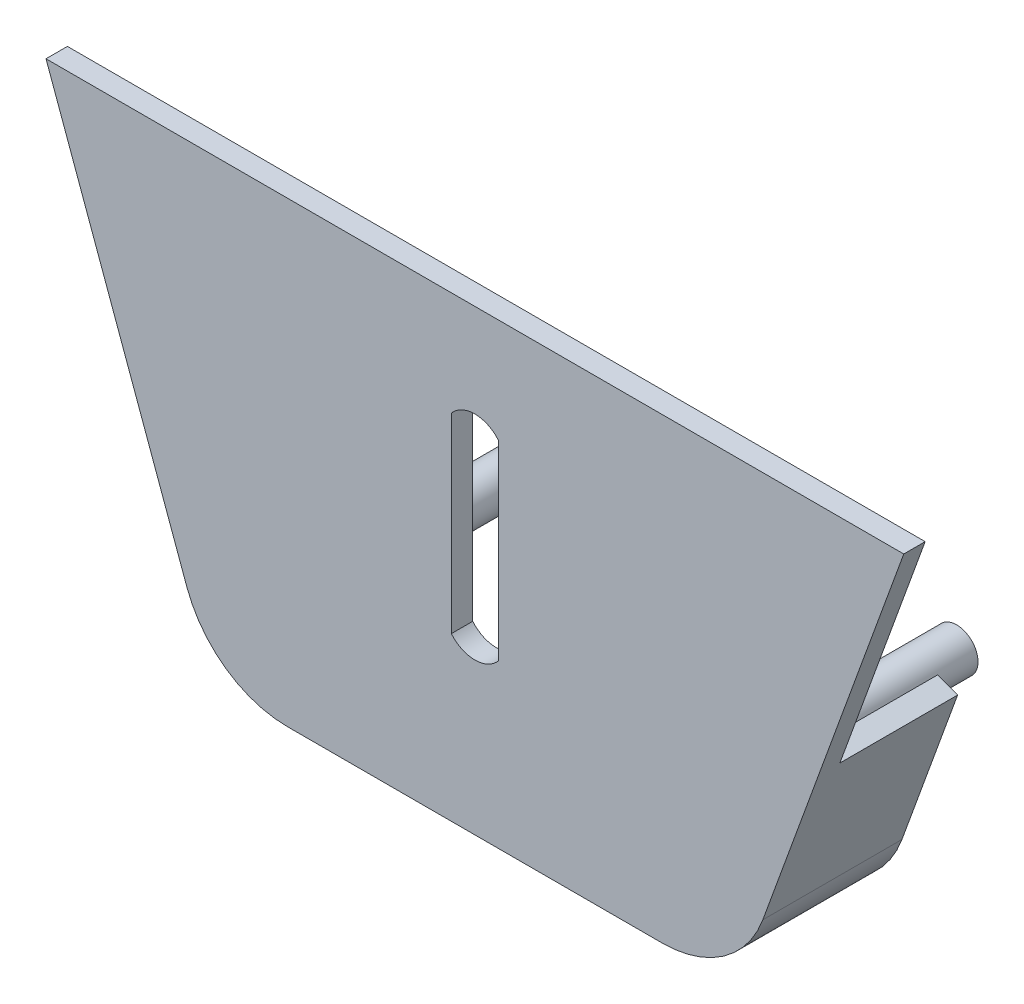
SolidWorks part; units mm, degrees
ref_plane "Front Plane" through (0, 0, 0) normal (0, 0, 1) x (1, 0, 0)
ref_plane "Top Plane" through (0, 0, 0) normal (0, 1, 0) x (1, 0, 0)
ref_plane "Right Plane" through (0, 0, 0) normal (1, 0, 0) x (0, 0, -1)
sketch "Sketch1" plane through (0, 0, 0) normal (0, 0, 1) x (1, 0, 0)
  line L0 (-17.5, 0) -> (17.5, 0) construction
  line L1 (-17.5, -10) -> (17.5, -10)
  line L2 (-26.8969, -3.4202) -> (-40.0654, 32.76)
  line L3 (-40.0654, 32.76) -> (40.0654, 32.76)
  line L4 (40.0654, 32.76) -> (26.8969, -3.4202)
  line L5 (40.0654, 32.76) -> (-40.0654, 32.76) construction
  line L6 (26.8969, -3.4202) -> (40.0654, 32.76) construction
  line L7 (-40.0654, 32.76) -> (-30.3893, 6.1749) construction
  line L8 (0, 21.1909) -> (0, 7.0144) construction
  line L9 (2.8635, 21.1909) -> (2.8635, 7.0144)
  line L10 (-2.8635, 21.1909) -> (-2.8635, 7.0144)
  arc A0 (-26.8969, -3.4202) -> (-17.5, -10) centre (-17.5, 0) ccw
  arc A1 (17.5, -10) -> (26.8969, -3.4202) centre (17.5, 0) ccw
  circle A2 centre (17.5, 0) radius 2 construction
  circle A3 centre (17.5, 0) radius 2
  circle A4 centre (-17.5, 0) radius 2 construction
  circle A5 centre (-17.5, 0) radius 2
  arc A6 (2.8635, 21.1909) -> (-2.8635, 21.1909) centre (0, 21.1909) ccw
  arc A9 (-2.8635, 7.0144) -> (2.8635, 7.0144) centre (0, 7.0144) ccw
  point P13 (0, 14.1027)
  dimension "D3" = 20
  dimension "D4" = 20
  dimension "D1" = 35
  dimension "D2" = 17.5
extrude "Boss-Extrude1" add sketch "Sketch1" along normal blind 2
sketch "Sketch2" plane through (0, 0, 2) normal (0, 0, 1) x (1, 0, 0)
  circle A0 centre (-17.5, 0) radius 2 construction
  circle A1 centre (-17.5, 0) radius 2
  circle A2 centre (-17.5, 0) radius 3.5
  circle A3 centre (17.5, 0) radius 2 construction
  circle A4 centre (17.5, 0) radius 2
  circle A5 centre (17.5, 0) radius 3.5
  dimension "D1" = 1.5
  dimension "D2" = 1.5
extrude "Boss-Extrude2" add sketch "Sketch2" against normal blind 4 from vertex starting at point (-17.5, -10, 0)
sketch "Sketch4" plane through (0, 0, 0) normal (0, 0, -1) x (-1, 0, 0)
  line L0 (-39.1029, 10.8636) -> (39.5724, 10.8636) construction
  line L1 (-26.8969, -3.4202) -> (-40.0654, 32.76) construction
  line L2 (-26.8969, -3.4202) -> (-32.0958, 10.8636)
  line L3 (40.0654, 32.76) -> (26.8969, -3.4202) construction
  line L4 (32.0958, 10.8636) -> (26.8969, -3.4202)
  line L5 (-25.0175, -2.7362) -> (-30.2164, 11.5477)
  line L6 (30.2164, 11.5477) -> (25.0175, -2.7362)
  line L7 (-32.0958, 10.8636) -> (-30.2164, 11.5477)
  line L8 (30.2164, 11.5477) -> (32.0958, 10.8636)
  line L9 (17.5, -8) -> (17.5, -10)
  line L10 (-17.5, -10) -> (-17.5, -8)
  arc A0 (-26.8969, -3.4202) -> (-17.5, -10) centre (-17.5, 0) ccw construction
  arc A1 (-26.8969, -3.4202) -> (-17.5, -10) centre (-17.5, 0) ccw
  arc A2 (17.5, -10) -> (26.8969, -3.4202) centre (17.5, 0) ccw construction
  arc A3 (17.5, -10) -> (26.8969, -3.4202) centre (17.5, 0) ccw
  arc A4 (-25.0175, -2.7362) -> (-17.5, -8) centre (-17.5, 0) ccw
  arc A5 (17.5, -8) -> (25.0175, -2.7362) centre (17.5, 0) ccw
  dimension "D1" = 2
  dimension "D2" = 2
extrude "Boss-Extrude3" add sketch "Sketch4" along normal blind 11
sketch "Sketch5" plane through (0, 0, 2) normal (0, 0, 1) x (1, 0, 0)
  circle A0 centre (-17.5, 0) radius 2 construction
  circle A1 centre (-17.5, 0) radius 2
  circle A2 centre (17.5, 0) radius 2 construction
  circle A3 centre (17.5, 0) radius 2
extrude "Boss-Extrude4" add sketch "Sketch5" against normal blind 16
sketch "Croquis3" plane through (0, 0, -14) normal (0, 0, -1) x (-1, 0, 0)
  circle A0 centre (-17.5, 0) radius 2
  circle A1 centre (17.5, 0) radius 2
extrude "Saliente-Extruir1" add sketch "Croquis3" along normal blind 10
sketch "Croquis4" plane through (0, 0, -24) normal (0, 0, -1) x (-1, 0, 0)
  circle A0 centre (-17.5, 0) radius 2
  circle A1 centre (17.5, 0) radius 2
extrude "Saliente-Extruir2" add sketch "Croquis4" along normal blind 1.5
sketch "Croquis5" plane through (0, 0, 2) normal (0, 0, 1) x (1, 0, 0)
  line L2 (0, 4.1509) -> (0, 24.0544) construction
  line L3 (-2.2, 4.1509) -> (-2.2, 24.0544)
  line L4 (2.2, 4.1509) -> (2.2, 24.0544)
  line L5 (2.8635, 7.0144) -> (2.8635, 21.1909) construction
  line L6 (-2.8635, 21.1909) -> (-2.8635, 7.0144) construction
  line L7 (2.8635, 7.0144) -> (2.8635, 21.1909)
  line L8 (-2.8635, 21.1909) -> (-2.8635, 7.0144)
  circle A0 centre (0, 14.7233) radius 2
  arc A1 (-2.8635, 7.0144) -> (2.8635, 7.0144) centre (0, 7.0144) ccw construction
  arc A2 (2.8635, 21.1909) -> (-2.8635, 21.1909) centre (0, 21.1909) ccw construction
  arc A3 (-2.2, 4.1509) -> (2.2, 4.1509) centre (0, 4.1509) ccw
  arc A4 (2.2, 24.0544) -> (-2.2, 24.0544) centre (0, 24.0544) ccw
  arc A5 (2.8635, 21.1909) -> (-2.8635, 21.1909) centre (0, 21.1909) ccw
  arc A6 (-2.8635, 7.0144) -> (2.8635, 7.0144) centre (0, 7.0144) ccw
  point P2 (0, 14.1027)
  line M7 (-2.8635, 7.0144) -> (-2.8635, 21.1909)
  arc M8 (-2.8635, 21.1909) -> (2.8635, 21.1909) centre (0, 21.1909) cw
  line M9 (2.8635, 21.1909) -> (2.8635, 7.0144)
  arc M10 (2.8635, 7.0144) -> (-2.8635, 7.0144) centre (0, 7.0144) cw
  dimension "D1" = 4
  dimension "D2" = 2.2
extrude "Saliente-Extruir3" add sketch "Croquis5" against normal up to surface (2 mm away) contours L3 M10 M8 M7 | L4 M10 M9 M8 region at (-2.5222, 14.1027, 2) region at (2.5222, 14.1027, 2) up to face at (21, 0, 0)
